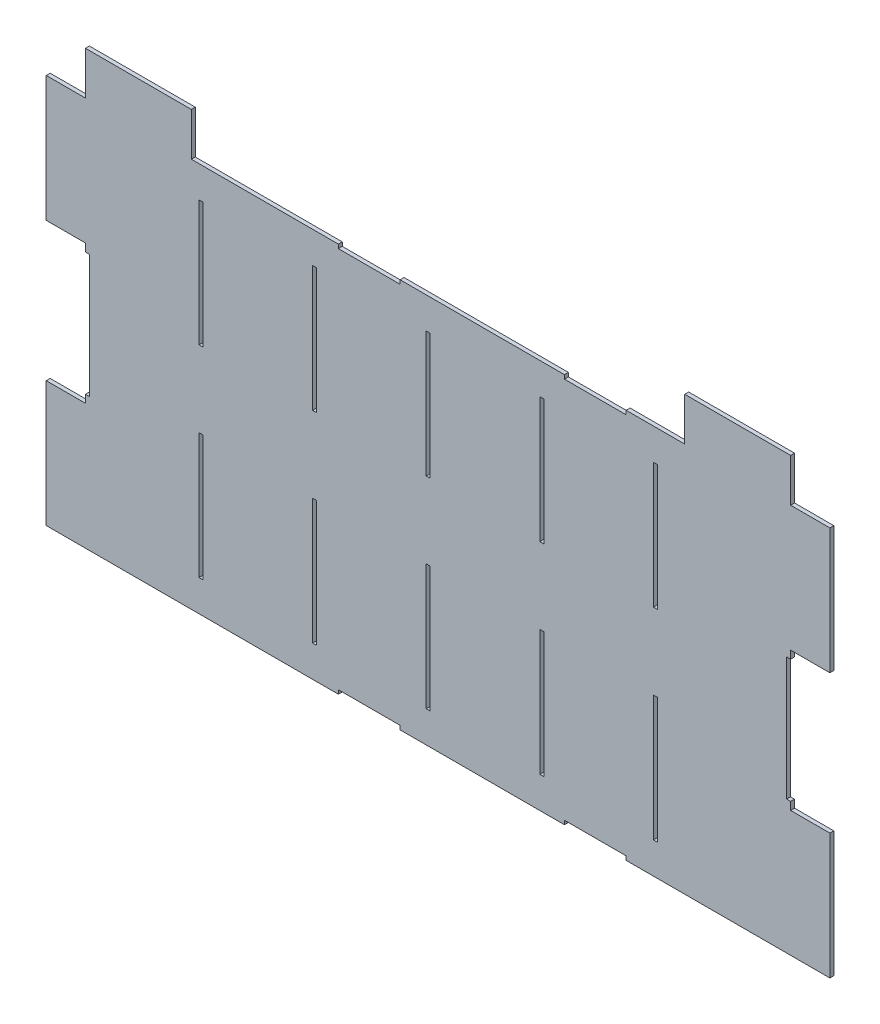
SolidWorks part; units mm, degrees
material "6061-T6 (SS)"
ref_plane "X-Y Datum" through (0, 0, 0) normal (0, 0, 1) x (1, 0, 0)
ref_plane "X-Z Datum" through (0, 0, 0) normal (0, 1, 0) x (1, 0, 0)
ref_plane "Y-Z Datum" through (0, 0, 0) normal (1, 0, 0) x (0, 0, -1)
sketch "Sketch1" plane through (0, 0, 0) normal (0, 0, 1) x (1, 0, 0)
  line L0 (-285.4305, 0) -> (285.4305, 0) construction
  line L1 (-285.4305, -157.7875) -> (285.4305, -157.7875)
  line L2 (-285.4305, -157.7875) -> (-285.4305, 157.7875)
  line L3 (-285.4305, 157.7875) -> (285.4305, 157.7875)
  line L4 (285.4305, -157.7875) -> (285.4305, 157.7875)
  line L5 (-285.4305, -157.7875) -> (285.4305, 157.7875) construction
  line L6 (-285.4305, 157.7875) -> (285.4305, -157.7875) construction
  line L7 (-282.2555, -154.615) -> (-282.2555, 154.615)
  line L8 (-280.6655, -153.025) -> (-195.0655, -153.025)
  line L9 (-280.6655, -153.025) -> (-280.6655, 153.025)
  line L10 (-280.6655, 153.025) -> (-195.0655, 153.025)
  line L11 (-195.0655, -153.025) -> (-195.0655, 153.025)
  line L12 (-280.6655, -153.025) -> (-195.0655, 153.025) construction
  line L13 (-280.6655, 153.025) -> (-195.0655, -153.025) construction
  line L14 (-282.2555, 154.615) -> (-193.4755, 154.615)
  line L15 (-193.4755, -154.615) -> (-193.4755, 154.615)
  line L16 (-282.2555, -154.615) -> (-193.4755, -154.615)
  line L17 (-190.3005, 154.615) -> (-101.5205, 154.615)
  line L18 (-188.7105, 153.025) -> (-103.1105, 153.025)
  line L19 (-190.3005, -154.615) -> (-190.3005, 154.615)
  line L20 (-188.7105, -153.025) -> (-188.7105, 153.025)
  line L21 (-101.5205, -154.615) -> (-101.5205, 154.615)
  line L22 (-103.1105, -153.025) -> (-103.1105, 153.025)
  line L23 (-188.7105, -153.025) -> (-103.1105, -153.025)
  line L24 (-190.3005, -154.615) -> (-101.5205, -154.615)
  line L25 (-188.7105, -153.025) -> (-103.1105, 153.025) construction
  line L26 (-188.7105, 153.025) -> (-103.1105, -153.025) construction
  line L27 (-98.3455, 154.615) -> (-9.5655, 154.615)
  line L28 (-96.7555, 153.025) -> (-11.1555, 153.025)
  line L29 (-98.3455, -154.615) -> (-98.3455, 154.615)
  line L30 (-96.7555, -153.025) -> (-96.7555, 153.025)
  line L31 (-9.5655, -154.615) -> (-9.5655, 154.615)
  line L32 (-11.1555, -153.025) -> (-11.1555, 153.025)
  line L33 (-96.7555, -153.025) -> (-11.1555, -153.025)
  line L34 (-98.3455, -154.615) -> (-9.5655, -154.615)
  line L35 (-96.7555, -153.025) -> (-11.1555, 153.025) construction
  line L36 (-96.7555, 153.025) -> (-11.1555, -153.025) construction
  line L37 (-6.3905, 154.615) -> (82.3895, 154.615)
  line L38 (-4.8005, 153.025) -> (80.7995, 153.025)
  line L39 (-6.3905, -154.615) -> (-6.3905, 154.615)
  line L40 (-4.8005, -153.025) -> (-4.8005, 153.025)
  line L41 (82.3895, -154.615) -> (82.3895, 154.615)
  line L42 (80.7995, -153.025) -> (80.7995, 153.025)
  line L43 (-4.8005, -153.025) -> (80.7995, -153.025)
  line L44 (-6.3905, -154.615) -> (82.3895, -154.615)
  line L45 (-4.8005, -153.025) -> (80.7995, 153.025) construction
  line L46 (-4.8005, 153.025) -> (80.7995, -153.025) construction
  line L47 (85.5645, 154.615) -> (174.3445, 154.615)
  line L48 (87.1545, 153.025) -> (172.7545, 153.025)
  line L49 (85.5645, -154.615) -> (85.5645, 154.615)
  line L50 (87.1545, -153.025) -> (87.1545, 153.025)
  line L51 (174.3445, -154.615) -> (174.3445, 154.615)
  line L52 (172.7545, -153.025) -> (172.7545, 153.025)
  line L53 (87.1545, -153.025) -> (172.7545, -153.025)
  line L54 (85.5645, -154.615) -> (174.3445, -154.615)
  line L55 (87.1545, -153.025) -> (172.7545, 153.025) construction
  line L56 (87.1545, 153.025) -> (172.7545, -153.025) construction
  point P0 (0, 0)
  point P8 (-237.8655, 0)
  point P17 (-145.9105, 0)
  dimension "D1" = 570.861
  dimension "D2" = 315.575
  dimension "D3" = 306.05
  dimension "D4" = 85.6
  dimension "D5" = 3.175
  dimension "D8" = 3.175
  dimension "D9" = 91.955
  dimension "D6" = 1.59
  dimension "D7" = 5
extrude "Boss-Extrude1" add sketch "Sketch1" along normal blind 3.175 contours L8 L11 L10 L9 | L20 L23 L22 L18 | L30 L33 L32 L28 | L50 L53 L52 L48 | L49 L54 L51 L47 L53 L50 L48 L52 | L1 L4 L3 L2 L54 L49 L47 L51 L44 L39 L37 L41 L34 L29 L27 L31 L24 L19 L17 L21 L16 L7 L14 L15 | L40 L43 L42 L38 | L7 L16 L15 L14 L11 L8 L9 L10 | L19 L24 L21 L17 L23 L20 L18 L22 | L29 L34 L31 L27 L33 L30 L28 L32 | L39 L44 L41 L37 L43 L40 L38 L42 region at (-284.7782, 0, 0) region at (-281.9338, 0, 0) region at (-237.8655, 0, 0) region at (-145.9105, 154.2933, 0) region at (-145.9105, 0, 0) region at (-53.9555, 154.2933, 0) region at (-53.9555, 0, 0) region at (37.9995, 154.2933, 0) region at (37.9995, 0, 0) region at (129.9545, 154.2933, 0) region at (129.9545, 0, 0)
sketch "Sketch2" plane through (0, 0, 3.175) normal (0, 0, 1) x (1, 0, 0)
  line L0 (-190.3005, -154.615) -> (-193.4755, -154.615) construction
  line L1 (-191.888, -154.615) -> (-191.888, 157.7875) construction
  line L2 (-285.4305, 157.7875) -> (285.4305, 157.7875) construction
  line L4 (-193.4755, -30.7875) -> (-190.3005, -30.7875)
  line L5 (-193.4755, -30.7875) -> (-193.4755, -132.3875)
  line L6 (-193.4755, -132.3875) -> (-190.3005, -132.3875)
  line L7 (-190.3005, -30.7875) -> (-190.3005, -132.3875)
  line L8 (-193.4755, -30.7875) -> (-190.3005, -132.3875) construction
  line L9 (-193.4755, -132.3875) -> (-190.3005, -30.7875) construction
  line L12 (-285.4305, -157.7875) -> (285.4305, -157.7875) construction
  point P8 (-191.888, -81.5875)
  dimension "D1" = 76.2
  dimension "D2" = 3.175
  dimension "D3" = 101.6
extrude "Cut-Extrude1" cut sketch "Sketch2" against normal blind 3.175
sketch "Sketch7" plane through (0, 0, 3.175) normal (0, 0, 1) x (1, 0, 0)
  line L0 (285.4305, -157.7875) -> (285.4305, 157.7875) construction
  line L1 (102.3049, -154.6125) -> (152.3049, -154.6125)
  line L2 (102.3049, -154.6125) -> (102.3049, -157.7875)
  line L3 (102.3049, -157.7875) -> (152.3049, -157.7875)
  line L4 (152.3049, -154.6125) -> (152.3049, -157.7875)
  line L5 (-80.6951, -154.6125) -> (-30.6951, -154.6125)
  line L6 (-80.6951, -154.6125) -> (-80.6951, -157.7875)
  line L7 (-80.6951, -157.7875) -> (-30.6951, -157.7875)
  line L8 (-30.6951, -154.6125) -> (-30.6951, -157.7875)
  dimension "D1" = 133
  dimension "D2" = 50
  dimension "D3" = 3.175
  dimension "D4" = 50
  dimension "D5" = 133.1256
extrude "Cut-Extrude5" cut sketch "Sketch7" against normal blind 3.175
mirror "Mirror3" about plane through (0, 0, 0) normal (0, 1, 0) of "Cut-Extrude1"
pattern_linear "LPattern2" count 5 spacing 91.96 along (1, 0, 0) of "Mirror3"
sketch "Sketch9" plane through (0, 0, 0) normal (0, 0, -1) x (-1, 0, 0)
  line L0 (-301.3055, -56.1875) -> (-301.3055, -157.7875) construction
  line L9 (-285.4305, 157.7875) -> (-199.7055, 157.7875)
  line L10 (-285.4305, 157.7875) -> (-285.4305, 192.7125)
  line L11 (-285.4305, 192.7125) -> (-199.7055, 192.7125)
  line L12 (-199.7055, 157.7875) -> (-199.7055, 192.7125)
  line L13 (-285.4305, 157.7875) -> (-317.1805, 157.7875)
  line L14 (-285.4305, 157.7875) -> (-285.4305, 56.1875)
  line L15 (-285.4305, 56.1875) -> (-317.1805, 56.1875)
  line L16 (-317.1805, 157.7875) -> (-317.1805, 56.1875)
  line L17 (-317.1805, 106.9875) -> (-285.4305, 106.9875) construction
  line L18 (-301.3055, 157.7875) -> (-301.3055, 113.3375)
  line L19 (-301.3055, 113.3375) -> (-301.3055, 56.1875) construction
  line L20 (-285.4305, -157.7875) -> (-317.1805, -157.7875)
  line L21 (-285.4305, -157.7875) -> (-285.4305, -88.7618)
  line L25 (-285.4305, -88.7618) -> (-285.4305, -56.1875)
  line L26 (-285.4305, -56.1875) -> (-317.1805, -56.1875)
  line L28 (-317.1805, -56.1875) -> (-317.1805, -157.7875)
  line L29 (-317.1805, -106.9875) -> (-285.4305, -106.9875) construction
  line L30 (-301.3055, -56.1875) -> (-301.3055, -106.9875) construction
  line L31 (-301.3055, -106.9875) -> (-301.3055, -157.7875) construction
  line L32 (-301.3055, -56.1875) -> (-301.3055, -106.9875) construction
  line L33 (-301.3055, -106.9875) -> (-301.3055, -157.7875) construction
  circle A0 centre (-301.3055, 135.5625) radius 3 construction
  circle A1 centre (-301.3055, 84.7625) radius 3 construction
  circle A2 centre (-301.3055, -81.5875) radius 3 construction
  circle A3 centre (-301.3055, -132.3875) radius 3 construction
  dimension "D1" = 6
  dimension "D2" = 6
  dimension "D3" = 85.725
  dimension "D4" = 34.925
  dimension "D5" = 101.6
  dimension "D6" = 31.75
  dimension "D7" = 31.75
  dimension "D8" = 101.6
extrude "Boss-Extrude3" add sketch "Sketch9" against normal blind 3.175 contours L13 L16 L15 L14 | L9 L12 L11 L10 | L26 L28 L20 L21 L25 A3 A2 region at (242.568, 175.25, 0) region at (301.3055, 106.9875, 0) region at (301.3055, -106.9875, 0)
mirror "Mirror4" about plane through (0, 0, 0) normal (1, 0, 0) of "Boss-Extrude3"
mirror "Mirror5" about plane through (0, 0, 0) normal (0, 1, 0) of "Cut-Extrude5"
sketch "Sketch10" plane through (0, 0, 0) normal (0, 0, -1) x (-1, 0, 0)
  line L0 (-285.4305, 56.1875) -> (-285.4305, 49.8375)
  line L1 (-285.4305, -56.1875) -> (-285.4305, 56.1875) construction
  line L2 (-285.4305, -56.1875) -> (-317.1805, -56.1875) construction
  line L3 (-285.4305, 49.8375) -> (-282.2555, 49.8375)
  line L4 (-285.4305, 49.8375) -> (-285.4305, -49.8375)
  line L5 (-285.4305, -49.8375) -> (-282.2555, -49.8375)
  line L6 (-282.2555, 49.8375) -> (-282.2555, -49.8375)
  line L7 (-285.4305, 56.1875) -> (-317.1805, 56.1875) construction
  dimension "D1" = 6.35
  dimension "D2" = 3.175
  dimension "D3" = 6.35
extrude "Cut-Extrude6" cut sketch "Sketch10" against normal through all contours L6 L3 L4 L5 region at (283.843, 0, 0)
mirror "Mirror6" about plane through (0, 0, 0) normal (1, 0, 0) of "Cut-Extrude6"
